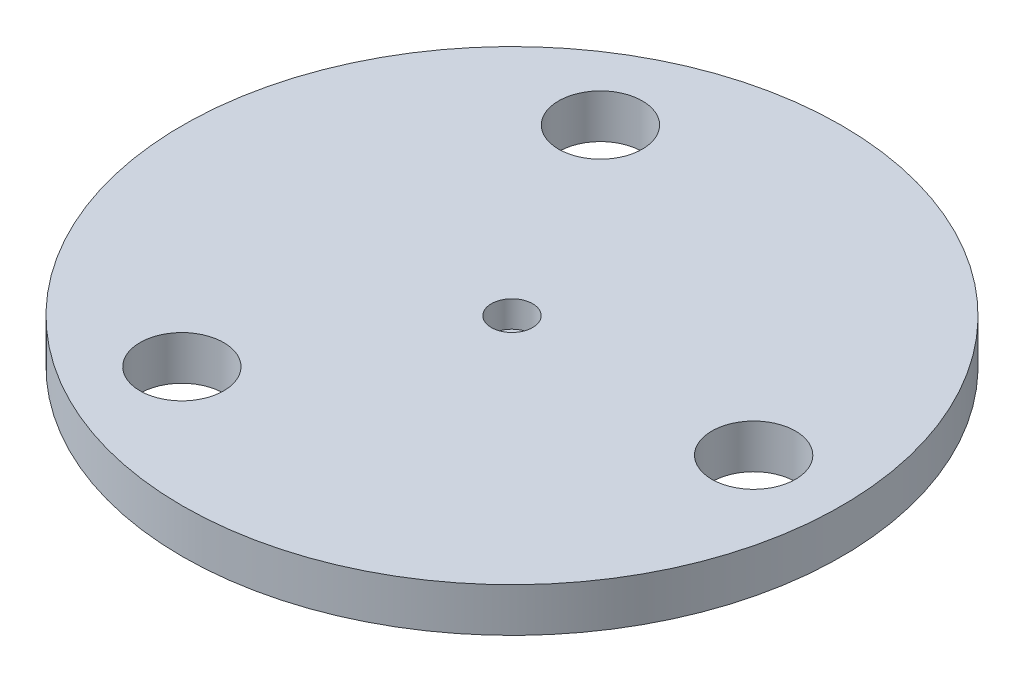
SolidWorks part; units mm, degrees
ref_plane "Front" through (0, 0, 0) normal (0, 0, 1) x (1, 0, 0)
ref_plane "Top" through (0, 0, 0) normal (0, 1, 0) x (1, 0, 0)
ref_plane "Right" through (0, 0, 0) normal (1, 0, 0) x (0, 0, -1)
sketch "Sketch1" plane through (0, 0, 0) normal (0, 1, 0) x (1, 0, 0)
  circle A0 centre (0, 0) radius 2.35
  circle A1 centre (0, 0) radius 37.5
  dimension "D1" = 4.7
  dimension "D2" = 75
extrude "Boss-Extrude1" add sketch "Sketch1" along normal blind 3 contours A1 A0 region at (-36.4393, 0, 0)
extrude "Boss-Extrude2" add sketch "Sketch1<3>" against normal blind 2 contours A0 | A1 A0 region at (0, 0, 0) region at (-36.4393, 0, 0)
sketch "Sketch1<3>" plane through (0, 0, 0) normal (0, 1, 0) x (1, 0, 0) same geometry as "Sketch1"
sketch "Sketch2" plane through (0, 3, 0) normal (0, 1, 0) x (1, 0, 0)
  line L0 (0, 0) -> (37.5, 0) construction
  circle A0 centre (0, 0) radius 37.5 construction
  circle A1 centre (27.5, 0) radius 4.7625
  dimension "D1" = 9.525
  dimension "D2" = 10
extrude "Cut-Extrude1" cut sketch "Sketch2" against normal through all contours A1
pattern_circular "CirPattern1" count 3 over 360 about axis through (0, 3, 0) along (0, 1, 0) of "Cut-Extrude1"
